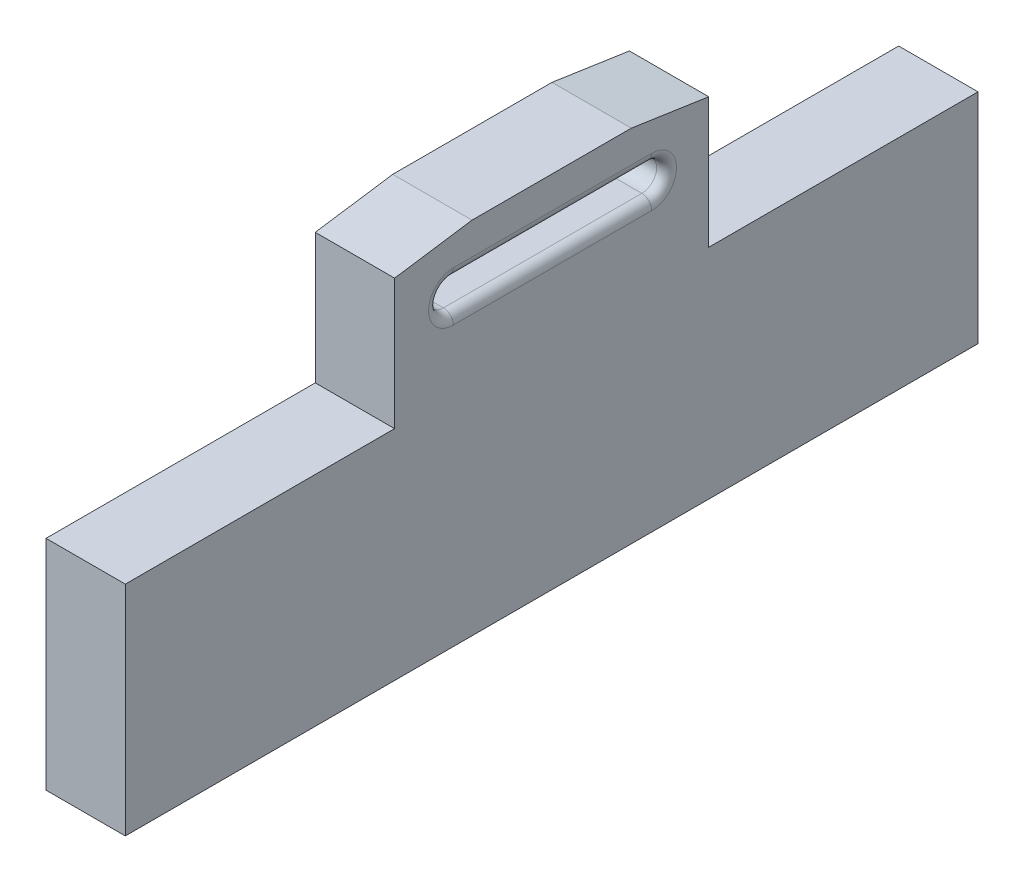
SolidWorks part; units mm, degrees
ref_plane "Спереди" through (0, 0, 0) normal (0, 0, 1) x (1, 0, 0)
ref_plane "Сверху" through (0, 0, 0) normal (0, 1, 0) x (1, 0, 0)
ref_plane "Справа" through (0, 0, 0) normal (1, 0, 0) x (0, 0, -1)
sketch "Эскиз1" plane through (0, 0, 0) normal (1, 0, 0) x (0, 0, -1)
  line L0 (43, 19.5) -> (43, 36.6774) construction
  line L2 (0, 14.3084) -> (86, 14.3084)
  line L3 (0, 14.3084) -> (0, -30.6125)
  line L4 (0, -30.6125) -> (86, -30.6125)
  line L5 (86, 14.3084) -> (86, -30.6125)
extrude "Вытянуть1" add sketch "Эскиз1" along normal blind 8
sketch "Эскиз3" plane through (0, 0, 0) normal (-1, 0, 0) x (0, 0, 1)
  line L0 (-43, 14.3875) -> (-43, 30.2119) construction
  line L1 (-86, -8.1125) -> (-126.279, -8.1125) construction
  line L2 (0, -30.6125) -> (0, -22)
  line L3 (-86, -30.6125) -> (-86, 14.3084) construction
  line L4 (0, -22) -> (-86, -22)
  line L5 (-86, -22) -> (-86, -30.6125)
  line L6 (0, 14.3875) -> (0, 0)
  line L7 (-27.1573, 13.148) -> (-35.5, 14.3875)
  line L8 (-35.5, 14.3875) -> (0, 14.3875)
  line L9 (0, 0) -> (-27.1573, 0)
  line L11 (-86, -30.6125) -> (0, -30.6125)
  line L12 (-58.8427, 0) -> (-58.8427, 13.148)
  line L13 (-86, 0) -> (-58.8427, 0)
  line L14 (-50.5, 14.3875) -> (-86, 14.3875)
  line L15 (-58.8427, 13.148) -> (-50.5, 14.3875)
  line L19 (-27.1573, 0) -> (-27.1573, 13.148)
  line L20 (-86, 14.3875) -> (-86, 0)
extrude "Вырез-Вытянуть2" cut sketch "Эскиз3" against normal through all
sketch "Эскиз4" plane through (0, 0, 0) normal (-1, 0, 0) x (0, 0, 1)
  line L0 (-79.6423, 8.585) -> (-0.7617, 8.585) construction
  line L1 (-43, 14.3875) -> (-43, 22.4896) construction
  line L2 (-53.0899, 10.085) -> (-33.0899, 10.085)
  line L3 (-53.0899, 7.085) -> (-33.0899, 7.085)
  arc A0 (-53.0899, 10.085) -> (-53.0899, 7.085) centre (-53.0899, 8.585) ccw
  arc A7 (-33.0899, 7.085) -> (-33.0899, 10.085) centre (-33.0899, 8.585) ccw
extrude "Вырез-Вытянуть3" cut sketch "Эскиз4" against normal through all
fillet "Скругление1" radius 1 8 edges at (8, 8.585, -31.5899) (8, 7.085, -43.0899) (8, 8.585, -54.5899) (0, 8.585, -31.5899) (0, 7.085, -43.0899) (0, 8.585, -54.5899) (8, 10.085, -43.0899) (0, 10.085, -43.0899)
